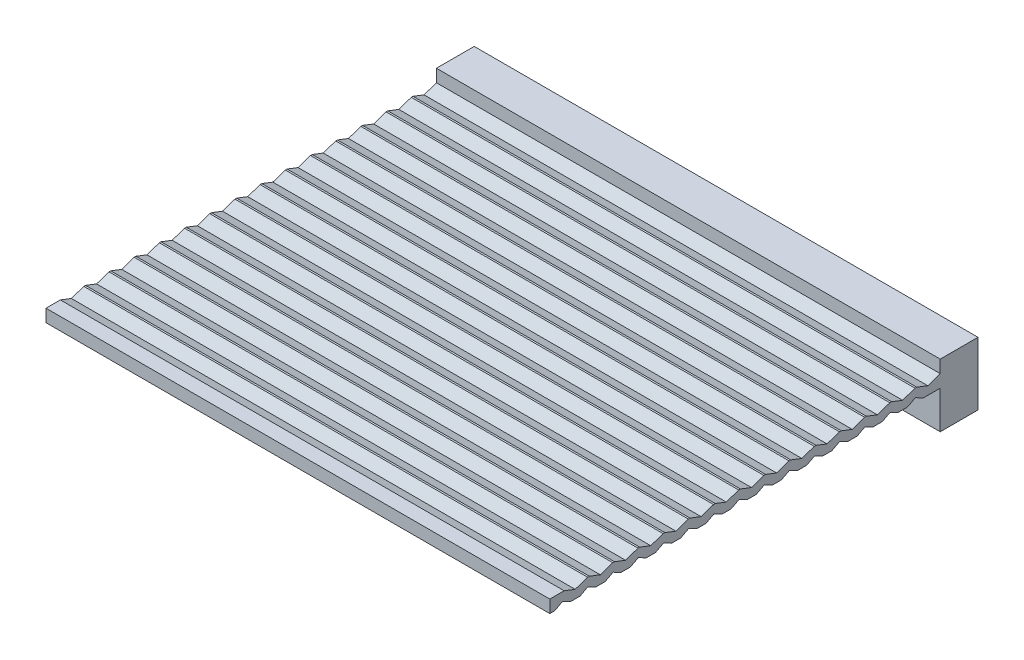
SolidWorks part; units mm, degrees
ref_plane "Front Plane" through (0, 0, 0) normal (0, 0, 1) x (1, 0, 0)
ref_plane "Top Plane" through (0, 0, 0) normal (0, 1, 0) x (1, 0, 0)
ref_plane "Right Plane" through (0, 0, 0) normal (1, 0, 0) x (0, 0, -1)
sketch "Sketch1" plane through (0, 0, 0) normal (0, 1, 0) x (1, 0, 0)
  line L1 (0, 0) -> (400, 0)
  line L2 (0, 0) -> (0, 30)
  line L3 (0, 30) -> (400, 30)
  line L4 (400, 0) -> (400, 30)
  dimension "D1" = 30
  dimension "D2" = 400
extrude "Boss-Extrude1" add sketch "Sketch1" along normal blind 50
sketch "Sketch2" plane through (0, 0, 0) normal (0, 0, 1) x (1, 0, 0)
  line L0 (0, 50) -> (400, 50) construction
  line L1 (0, 40) -> (400, 40)
  line L2 (0, 40) -> (0, 30)
  line L3 (0, 30) -> (400, 30)
  line L4 (400, 40) -> (400, 30)
  line L5 (0, 50) -> (0, 0) construction
  line L6 (400, 50) -> (400, 0) construction
  dimension "D1" = 10
  dimension "D2" = 10
extrude "Boss-Extrude2" add sketch "Sketch2" along normal blind 310
sketch "Sketch3" plane through (0, 0, 0) normal (-1, 0, 0) x (0, 0, 1)
  line L0 (0, 40) -> (9.8674, 36.6243)
  line L1 (9.8674, 36.6243) -> (18.6179, 40)
  line L2 (310, 40) -> (0, 40) construction
  line L3 (18.6179, 40) -> (0, 40)
  line L4 (13.2834, 30) -> (19.7384, 33.3028)
  line L5 (310, 30) -> (0, 30) construction
  line L6 (19.7384, 33.3028) -> (26.0128, 30)
  line L7 (26.0128, 30) -> (13.2834, 30)
extrude "Cut-Extrude1" cut sketch "Sketch3" against normal up to next
pattern_linear "LPattern1" count 15 spacing 20 along (0, 0, 1) of "Cut-Extrude1"
